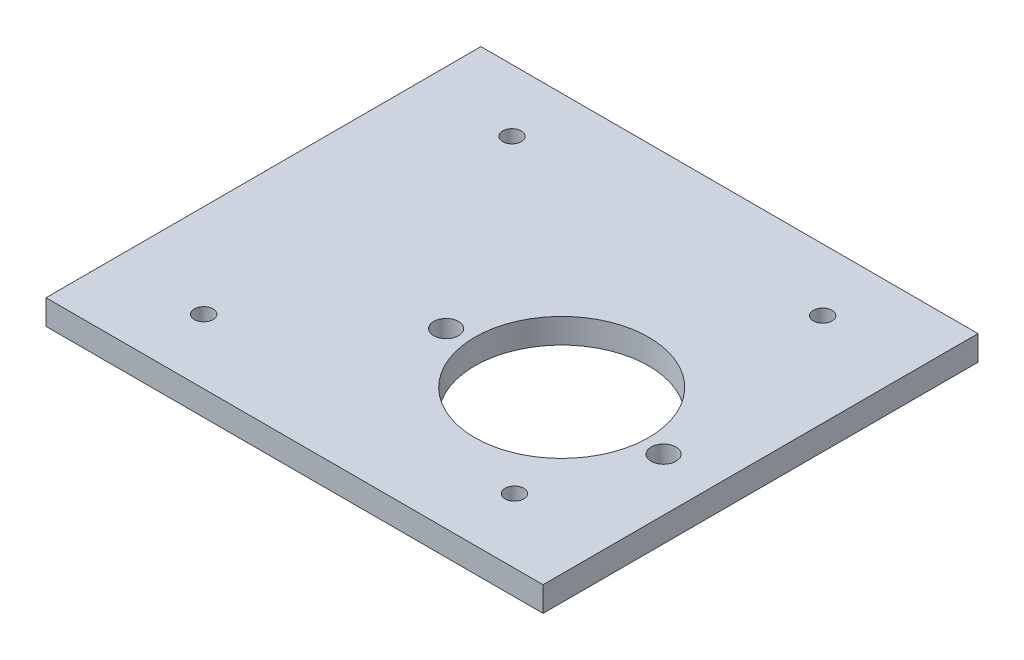
SolidWorks part; units mm, degrees
ref_plane "Front Plane" through (0, 0, 0) normal (0, 0, 1) x (1, 0, 0)
ref_plane "Top Plane" through (0, 0, 0) normal (0, 1, 0) x (1, 0, 0)
ref_plane "Right Plane" through (0, 0, 0) normal (1, 0, 0) x (0, 0, -1)
sketch "Sketch1" plane through (0, 0, 0) normal (0, 1, 0) x (1, 0, 0)
  line L0 (0, 8.2993) -> (0, -7.906) construction
  line L1 (-40, 35) -> (40, 35)
  line L2 (-40, 35) -> (-40, -35)
  line L3 (-40, -35) -> (40, -35)
  line L4 (40, 35) -> (40, -35)
  line L5 (-40, 35) -> (40, -35) construction
  line L6 (-40, -35) -> (40, 35) construction
  line L7 (-14.9915, 0.1967) -> (11.9413, 0.1967) construction
  line L9 (35.0085, 0.1967) -> (61.9413, 0.1967) construction
  line L11 (12.5001, 2.9838) -> (12.5001, -1.0162)
  line L13 (15.4999, 3.0162) -> (15.4999, -0.9838)
  line L14 (12.5001, 2.9838) -> (15.4999, -0.9838) construction
  line L15 (12.5001, -1.0162) -> (15.4999, 3.0162) construction
  circle A0 centre (-25, 25) radius 1.5
  circle A1 centre (25, 25) radius 1.5
  circle A2 centre (25, -24.6067) radius 1.5
  circle A3 centre (-25, -24.6067) radius 1.5
  circle A4 centre (14, 1) radius 10
  circle A5 centre (-16, 1) radius 20
  arc A6 (12.5001, 2.9838) -> (15.4999, 3.0162) centre (14.0217, 1.0001) cw
  arc A7 (12.5001, -1.0162) -> (15.4999, -0.9838) centre (13.9783, 0.9999) ccw
  circle A8 centre (13.9783, 0.9999) radius 4.5
  circle A9 centre (14, -6) radius 14
  circle A10 centre (-3.5, -7.1027) radius 2
  circle A11 centre (31.5, -7.1027) radius 2
  point P0 (0, 0)
  dimension "D3" = 15
  dimension "D6" = 3
  dimension "D7" = 26
  dimension "D10" = 20
  dimension "D11" = 9
  dimension "D12" = 7
  dimension "D13" = 17.5
  dimension "D14" = 4
  dimension "D15" = 4
  dimension "D17" = 40
  dimension "D1" = 80
  dimension "D2" = 70
  dimension "D4" = 10
  dimension "D8" = 4
  dimension "D9" = 3
  dimension "D16" = 17.5
  dimension "D18" = 36
  dimension "D19" = 4
  dimension "D5" = 2
extrude "Boss-Extrude4" add sketch "Sketch1" along normal blind 4 contours L4 L1 L2 L3 A11 A9 A4 A5 A2 A1 A0 A3 | A9 A5 A10 | A9 A4 region at (0, 0, -33.937) region at (14, 0, -8.4705) region at (-16.5796, 0, -1.1889)
